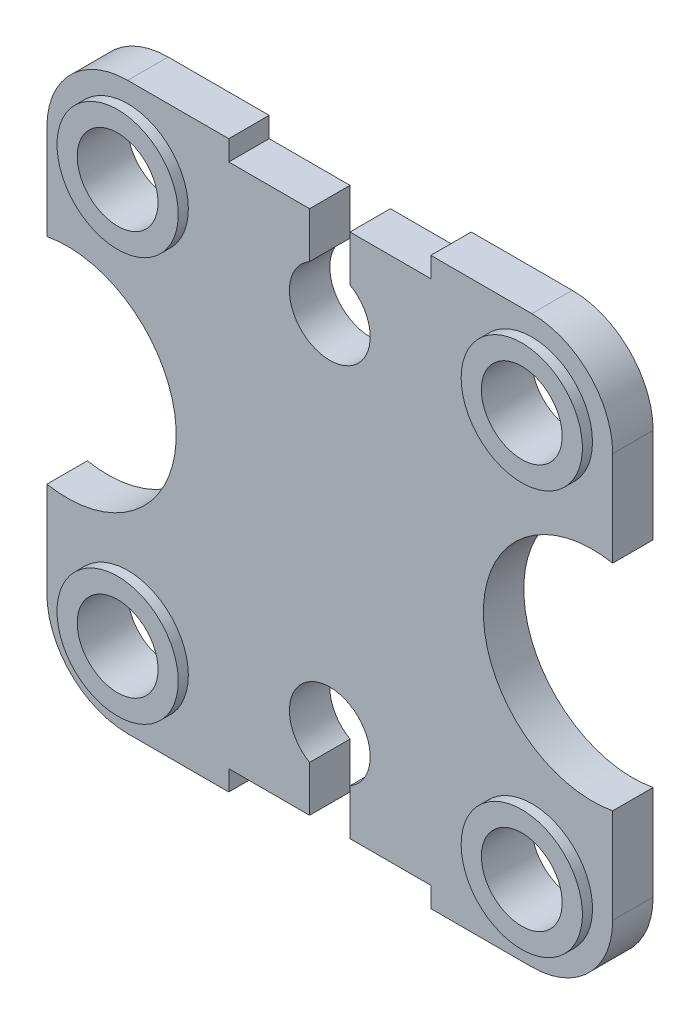
SolidWorks part; units mm, degrees
ref_plane "Front Plane" through (0, 0, 0) normal (0, 0, 1) x (1, 0, 0)
ref_plane "Top Plane" through (0, 0, 0) normal (0, 1, 0) x (1, 0, 0)
ref_plane "Right Plane" through (0, 0, 0) normal (1, 0, 0) x (0, 0, -1)
sketch "Sketch1" plane through (0, 0, 0) normal (0, 0, 1) x (1, 0, 0)
  line L0 (-140, 0) -> (140, 0) construction
  line L1 (0, 110.8611) -> (0, -110.8611) construction
  line L2 (-140, 100) -> (-140, 53.066)
  line L3 (-100, 140) -> (-50, 140)
  line L4 (-50, 140) -> (-50, 130)
  line L5 (-50, 130) -> (-10, 130)
  line L6 (-10, 130) -> (-10, 107.3205)
  line L7 (-76, 0) -> (0, 0)
  line L8 (0, 0) -> (0, 70)
  circle A0 centre (-100, 100) radius 20
  circle A4 centre (-100, 100) radius 30
  arc A5 (-100, 140) -> (-140, 100) centre (-100, 100) ccw
  arc A7 (-10, 107.3205) -> (0, 70) centre (0, 90) ccw
  arc A8 (-76, 0) -> (-140, 53.066) centre (-130, 0) ccw
  point P4 (0, 0)
  point P8 (0, 0)
  dimension "D1" = 40
  dimension "D2" = 60
  dimension "D3" = 80
  dimension "D5" = 108
  dimension "D6" = 40
  dimension "D4" = 100
  dimension "D7" = 100
  dimension "D8" = 90
  dimension "D10" = 10
  dimension "D11" = 40
  dimension "D12" = 50
extrude "Boss-Extrude3" add sketch "Sketch1" along normal blind 20 contours L2 A8 L7 L8 A7 L6 L5 L4 L3 A5 | A4
extrude "Boss-Extrude4" add sketch "Sketch1<3>" along normal blind 25 contours A0 | A4
sketch "Sketch1<3>" plane through (0, 0, 0) normal (0, 0, 1) x (1, 0, 0) same geometry as "Sketch1"
mirror "Mirror1" about plane through (0, 0, 0) normal (1, 0, 0) of "Boss-Extrude4", "Boss-Extrude3" second plane through (0, 0, 0) second plane normal (0, 1, 0)
